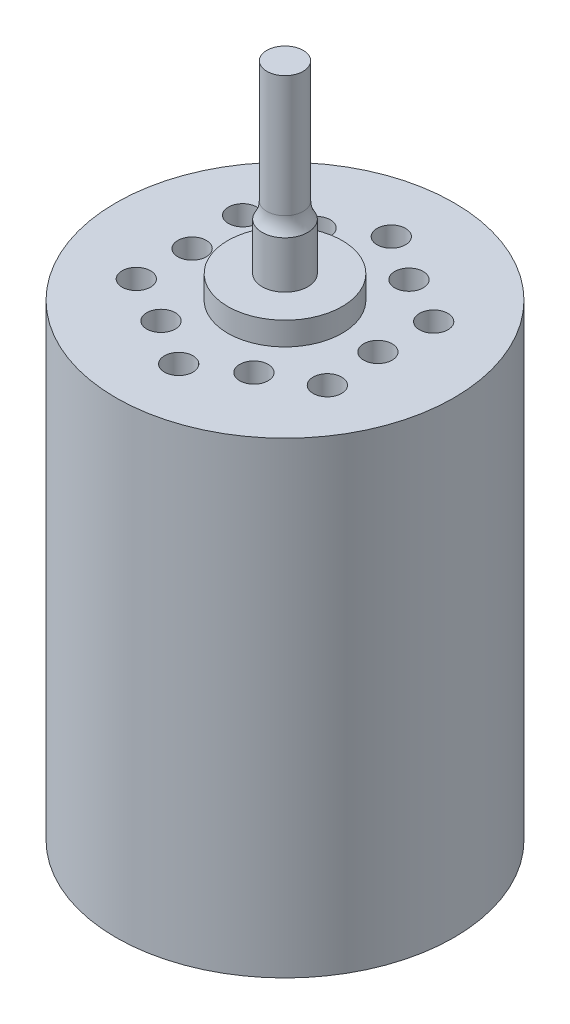
SolidWorks part; units mm, degrees
ref_plane "Front Plane" through (0, 0, 0) normal (0, 0, 1) x (1, 0, 0)
ref_plane "Top Plane" through (0, 0, 0) normal (0, 1, 0) x (1, 0, 0)
ref_plane "Right Plane" through (0, 0, 0) normal (1, 0, 0) x (0, 0, -1)
sketch "Sketch1" plane through (0, 0, 0) normal (0, 1, 0) x (1, 0, 0)
  circle A0 centre (0, 0) radius 14.8209
  dimension "D1" = 29.6418
extrude "Boss-Extrude1" add sketch "Sketch1" along normal blind 40.9956
sketch "Sketch2" plane through (0, 40.9956, 0) normal (0, 1, 0) x (1, 0, 0)
  circle A0 centre (0, 0) radius 5.0165
  dimension "D1" = 10.033
extrude "Boss-Extrude2" add sketch "Sketch2" along normal blind 2.032
sketch "Sketch3" plane through (0, 43.0276, 0) normal (0, 1, 0) x (1, 0, 0)
  circle A0 centre (0, 0) radius 2.0066
  dimension "D1" = 4.0132
extrude "Boss-Extrude3" add sketch "Sketch3" along normal blind 4.1275
sketch "Sketch4" plane through (0, 47.1551, 0) normal (0, 1, 0) x (1, 0, 0)
  circle A0 centre (0, 0) radius 1.5939
  dimension "D1" = 3.1877
extrude "Boss-Extrude4" add sketch "Sketch4" along normal blind 12.0269
fillet "Fillet1" radius 2.54 1 edges at (0, 47.1551, 1.5939)
sketch "Sketch5" plane through (0, 40.9956, 0) normal (0, 1, 0) x (1, 0, 0)
  line L0 (0, 0) -> (-4.1272, 6.8532) construction
  line L1 (-0.1754, 9.4984) -> (-8.3135, 4.5973) construction
  line L2 (-8.3135, 4.5973) -> (-8.1382, -4.9011) construction
  line L3 (-8.1382, -4.9011) -> (0.1754, -9.4984) construction
  line L4 (0.1754, -9.4984) -> (8.3135, -4.5973) construction
  line L5 (8.3135, -4.5973) -> (8.1382, 4.9011) construction
  line L6 (8.1382, 4.9011) -> (-0.1754, 9.4984) construction
  line L7 (-4.1272, 6.8532) -> (-7.9986, -0.1477) construction
  line L8 (-7.9986, -0.1477) -> (-3.8714, -7.0009) construction
  line L9 (-3.8714, -7.0009) -> (4.1272, -6.8532) construction
  line L10 (4.1272, -6.8532) -> (7.9986, 0.1477) construction
  line L11 (7.9986, 0.1477) -> (3.8714, 7.0009) construction
  line L12 (3.8714, 7.0009) -> (-4.1272, 6.8532) construction
  line L13 (0, 0) -> (8.1382, 4.9011) construction
  circle A0 centre (0, 0) radius 8.2272 construction
  circle A1 centre (0, 0) radius 6.9282 construction
  circle A2 centre (-0.1754, 9.4984) radius 1.25
  circle A3 centre (3.8714, 7.0009) radius 1.25
  circle A4 centre (8.1382, 4.9011) radius 1.25
  circle A5 centre (7.9986, 0.1477) radius 1.25
  circle A6 centre (8.3135, -4.5973) radius 1.25
  circle A7 centre (0.1754, -9.4984) radius 1.25
  circle A8 centre (-3.8714, -7.0009) radius 1.25
  circle A9 centre (-8.1382, -4.9011) radius 1.25
  circle A10 centre (-7.9986, -0.1477) radius 1.25
  circle A11 centre (-4.1272, 6.8532) radius 1.25
  circle A12 centre (-8.3135, 4.5973) radius 1.25
  circle A13 centre (4.1272, -6.8532) radius 1.25
  dimension "D4" = 2.5
  dimension "D1" = 19
  dimension "D2" = 90
  dimension "D3" = 16
extrude "Cut-Extrude1" cut sketch "Sketch5" against normal blind 3.175
sketch "Sketch6" plane through (0, 37.8206, 0) normal (0, 1, 0) x (1, 0, 0)
  circle A0 centre (0, 0) radius 14.4272
  circle A1 centre (0, 0) radius 14.8209 construction
  dimension "D1" = 0.3937
extrude "Cut-Extrude2" cut sketch "Sketch6" against normal blind 35.56
